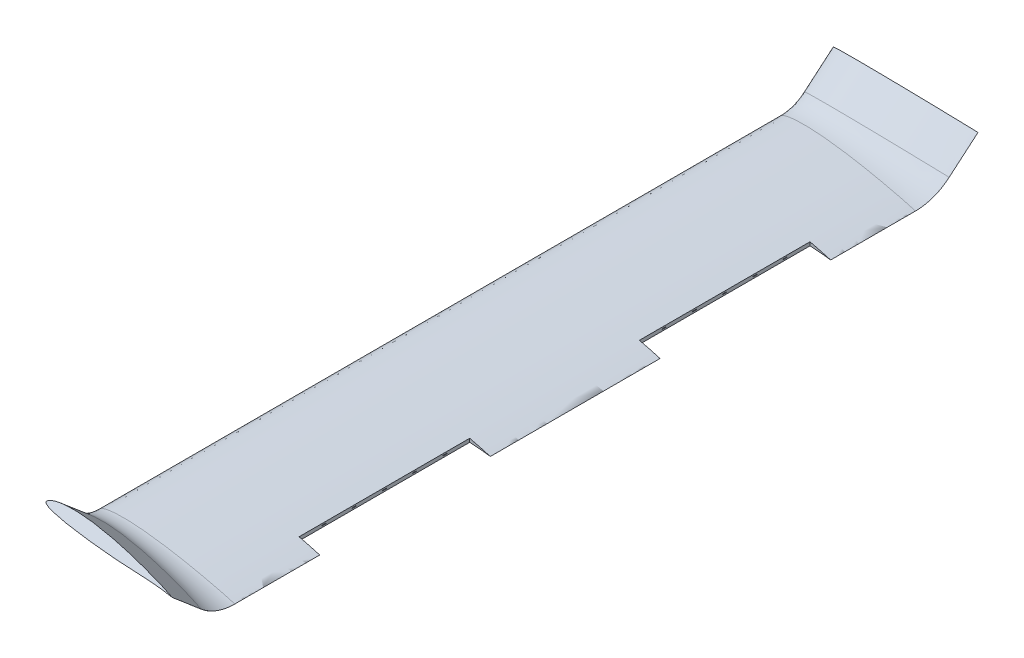
SolidWorks part; units mm, degrees
material "Bambu PETG Basic"
ref_plane "Front Plane" through (0, 0, 0) normal (0, 0, 1) x (1, 0, 0)
ref_plane "Top Plane" through (0, 0, 0) normal (0, 1, 0) x (1, 0, 0)
ref_plane "Right Plane" through (0, 0, 0) normal (1, 0, 0) x (0, 0, -1)
curve "Curve1"
  spline degree 3 poles (119.1315, 0.0649, 0) (120.2156, -0.0244, 0) (119.1768, 0.1241, 0) (118.3611, 0.3045, 0) (116.4409, 0.6648, 0) (114.1217, 1.0784, 0) (111.1249, 1.5376, 0) (107.6046, 2.0509, 0) (103.5602, 2.608, 0) (99.06, 3.1954, 0) (94.1552, 3.7992, 0) (88.9062, 4.4027, 0) (83.3727, 4.9915, 0) (77.618, 5.549, 0) (71.7044, 6.061, 0) (65.6958, 6.5098, 0) (59.6548, 6.8864, 0) (53.6439, 7.1734, 0) (47.7232, 7.3639, 0) (41.951, 7.4465, 0) (36.3826, 7.4159, 0) (31.0697, 7.2693, 0) (26.0605, 7.0029, 0) (21.3986, 6.6205, 0) (17.1237, 6.1259, 0) (13.271, 5.5293, 0) (9.8698, 4.8453, 0) (6.9483, 4.0868, 0) (4.5212, 3.2757, 0) (2.6143, 2.4295, 0) (1.2014, 1.5823, 0) (0.3641, 0.7994, 0) (-0.0092, 0.2127, 0) (0.0098, -0.2759, 0) (0.5281, -0.822, 0) (1.6534, -1.2926, 0) (3.3836, -1.8053, 0) (5.6974, -2.226, 0) (8.5941, -2.5892, 0) (12.0482, -2.8762, 0) (16.0312, -3.0928, 0) (20.503, -3.242, 0) (25.4176, -3.3266, 0) (30.7212, -3.3509, 0) (36.3546, -3.3217, 0) (42.254, -3.2414, 0) (48.3509, -3.1139, 0) (54.5739, -2.9419, 0) (60.8492, -2.7246, 0) (67.1164, -2.4479, 0) (73.3283, -2.0718, 0) (79.4439, -1.6435, 0) (85.4067, -1.2207, 0) (91.1384, -0.83, 0) (96.5553, -0.4959, 0) (101.5728, -0.229, 0) (106.1163, -0.0388, 0) (110.0944, 0.0802, 0) (113.4911, 0.1249, 0) (116.1071, 0.1318, 0) (118.2476, 0.0764, 0) (119.1315, 0.0649, 0) (120.2156, -0.0244, 0) (119.1768, 0.1241, 0) knots -0.014822 -0.00667 -0.001684 0 0.001648 0.006398 0.013891 0.023874 0.036301 0.051055 0.067935 0.086711 0.107144 0.128994 0.151997 0.175902 0.200434 0.225339 0.250352 0.275221 0.299694 0.323544 0.346547 0.368496 0.38921 0.408523 0.426284 0.442373 0.456684 0.46913 0.479656 0.488244 0.494928 0.499769 0.502616 0.502853 0.505768 0.510839 0.518187 0.527885 0.539915 0.554232 0.570707 0.589198 0.609515 0.631441 0.65473 0.679124 0.704341 0.730082 0.756046 0.781927 0.807595 0.83294 0.857679 0.881457 0.903929 0.924736 0.943553 0.960078 0.974032 0.985178 0.99333 0.998316 1 1.001648 1.006398 1.013891 periodic
sketch "Sketch2" plane through (0, 0, 0) normal (0, 0, 1) x (1, 0, 0)
  line L0 (0, 0) -> (119.3426, -12.5434) construction
  spline S2 degree 3 poles (147.8928, -15.4463) (149.4961, -15.7494) (147.9697, -15.3651) (146.7812, -14.9681) (143.9731, -14.1295) (140.5782, -13.1489) (136.1796, -11.994) (131.0085, -10.6763) (125.0626, -9.2111) (118.4414, -7.6292) (111.2191, -5.9594) (103.4834, -4.2361) (95.3209, -2.4902) (86.8235, -0.7562) (78.0821, 0.9348) (69.1889, 2.5464) (60.2361, 4.0555) (51.3141, 5.4261) (42.5116, 6.6385) (33.9137, 7.6667) (25.602, 8.4943) (17.6534, 9.1085) (10.1389, 9.4965) (3.1245, 9.6571) (-3.3303, 9.5895) (-9.1713, 9.3035) (-14.3523, 8.8165) (-18.8295, 8.143) (-22.5773, 7.3137) (-25.5548, 6.3502) (-27.7953, 5.308) (-29.1672, 4.2712) (-29.816, 3.4545) (-29.8643, 2.7228) (-29.1767, 1.8267) (-27.5718, 0.9483) (-25.0711, -0.0878) (-21.6854, -1.0781) (-17.421, -2.0741) (-12.3134, -3.0439) (-6.4055, -3.9916) (0.2421, -4.9153) (7.5604, -5.8121) (15.4683, -6.6798) (23.8767, -7.5195) (32.6899, -8.3247) (41.8052, -9.0905) (51.1155, -9.8097) (60.511, -10.4694) (69.9037, -11.0393) (79.2294, -11.4522) (88.4197, -11.7722) (97.3811, -12.0763) (105.9929, -12.3922) (114.1262, -12.7431) (121.653, -13.1316) (128.4607, -13.5603) (134.4139, -14.0065) (139.4881, -14.4724) (143.3916, -14.8723) (146.5761, -15.2905) (147.8928, -15.4463) (149.4961, -15.7494) (147.9697, -15.3651) knots -0.014822 -0.00667 -0.001684 0 0.001648 0.006398 0.013891 0.023874 0.036301 0.051055 0.067935 0.086711 0.107144 0.128994 0.151997 0.175902 0.200434 0.225339 0.250352 0.275221 0.299694 0.323544 0.346547 0.368496 0.38921 0.408523 0.426284 0.442373 0.456684 0.46913 0.479656 0.488244 0.494928 0.499769 0.502616 0.502853 0.505768 0.510839 0.518187 0.527885 0.539915 0.554232 0.570707 0.589198 0.609515 0.631441 0.65473 0.679124 0.704341 0.730082 0.756046 0.781927 0.807595 0.83294 0.857679 0.881457 0.903929 0.924736 0.943553 0.960078 0.974032 0.985178 0.99333 0.998316 1 1.001648 1.006398 1.013891 only from (149.1783, -15.6793) to (149.1783, -15.6793)
  point P1 (-29.8357, 3.1359)
extrude "Boss-Extrude1" add sketch "Sketch2" along normal blind 450 and the other way blind 450
ref_plane "Plane5" through (-29.8357, 0, 0) normal (1, 0, 0) x (0, 0, -1)
sketch "Sketch4" plane through (0, 0, 450) normal (0, 0, 1) x (1, 0, 0)
  spline S1 degree 3 poles (147.8928, -15.4463) (149.4961, -15.7494) (147.9697, -15.3651) (146.7812, -14.9681) (143.9731, -14.1295) (140.5782, -13.1489) (136.1796, -11.994) (131.0085, -10.6763) (125.0626, -9.2111) (118.4414, -7.6292) (111.2191, -5.9594) (103.4834, -4.2361) (95.3209, -2.4902) (86.8235, -0.7562) (78.0821, 0.9348) (69.1889, 2.5464) (60.2361, 4.0555) (51.3141, 5.4261) (42.5116, 6.6385) (33.9137, 7.6667) (25.602, 8.4943) (17.6534, 9.1085) (10.1389, 9.4965) (3.1245, 9.6571) (-3.3303, 9.5895) (-9.1713, 9.3035) (-14.3523, 8.8165) (-18.8295, 8.143) (-22.5773, 7.3137) (-25.5548, 6.3502) (-27.7953, 5.308) (-29.1672, 4.2712) (-29.816, 3.4545) (-29.8643, 2.7228) (-29.1767, 1.8267) (-27.5718, 0.9483) (-25.0711, -0.0878) (-21.6854, -1.0781) (-17.421, -2.0741) (-12.3134, -3.0439) (-6.4055, -3.9916) (0.2421, -4.9153) (7.5604, -5.8121) (15.4683, -6.6798) (23.8767, -7.5195) (32.6899, -8.3247) (41.8052, -9.0905) (51.1155, -9.8097) (60.511, -10.4694) (69.9037, -11.0393) (79.2294, -11.4522) (88.4197, -11.7722) (97.3811, -12.0763) (105.9929, -12.3922) (114.1262, -12.7431) (121.653, -13.1316) (128.4607, -13.5603) (134.4139, -14.0065) (139.4881, -14.4724) (143.3916, -14.8723) (146.5761, -15.2905) (147.8928, -15.4463) (149.4961, -15.7494) (147.9697, -15.3651) knots -0.014822 -0.00667 -0.001684 0 0.001648 0.006398 0.013891 0.023874 0.036301 0.051055 0.067935 0.086711 0.107144 0.128994 0.151997 0.175902 0.200434 0.225339 0.250352 0.275221 0.299694 0.323544 0.346547 0.368496 0.38921 0.408523 0.426284 0.442373 0.456684 0.46913 0.479656 0.488244 0.494928 0.499769 0.502616 0.502853 0.505768 0.510839 0.518187 0.527885 0.539915 0.554232 0.570707 0.589198 0.609515 0.631441 0.65473 0.679124 0.704341 0.730082 0.756046 0.781927 0.807595 0.83294 0.857679 0.881457 0.903929 0.924736 0.943553 0.960078 0.974032 0.985178 0.99333 0.998316 1 1.001648 1.006398 1.013891 only from (149.1783, -15.6793) to (149.1783, -15.6793)
  spline S3 degree 3 poles (147.8928, -15.4463) (149.4961, -15.7494) (147.9697, -15.3651) (146.7812, -14.9681) (143.9731, -14.1295) (140.5782, -13.1489) (136.1796, -11.994) (131.0085, -10.6763) (125.0626, -9.2111) (118.4414, -7.6292) (111.2191, -5.9594) (103.4834, -4.2361) (95.3209, -2.4902) (86.8235, -0.7562) (78.0821, 0.9348) (69.1889, 2.5464) (60.2361, 4.0555) (51.3141, 5.4261) (42.5116, 6.6385) (33.9137, 7.6667) (25.602, 8.4943) (17.6534, 9.1085) (10.1389, 9.4965) (3.1245, 9.6571) (-3.3303, 9.5895) (-9.1713, 9.3035) (-14.3523, 8.8165) (-18.8295, 8.143) (-22.5773, 7.3137) (-25.5548, 6.3502) (-27.7953, 5.308) (-29.1672, 4.2712) (-29.816, 3.4545) (-29.8643, 2.7228) (-29.1767, 1.8267) (-27.5718, 0.9483) (-25.0711, -0.0878) (-21.6854, -1.0781) (-17.421, -2.0741) (-12.3134, -3.0439) (-6.4055, -3.9916) (0.2421, -4.9153) (7.5604, -5.8121) (15.4683, -6.6798) (23.8767, -7.5195) (32.6899, -8.3247) (41.8052, -9.0905) (51.1155, -9.8097) (60.511, -10.4694) (69.9037, -11.0393) (79.2294, -11.4522) (88.4197, -11.7722) (97.3811, -12.0763) (105.9929, -12.3922) (114.1262, -12.7431) (121.653, -13.1316) (128.4607, -13.5603) (134.4139, -14.0065) (139.4881, -14.4724) (143.3916, -14.8723) (146.5761, -15.2905) (147.8928, -15.4463) (149.4961, -15.7494) (147.9697, -15.3651) knots -0.014822 -0.00667 -0.001684 0 0.001648 0.006398 0.013891 0.023874 0.036301 0.051055 0.067935 0.086711 0.107144 0.128994 0.151997 0.175902 0.200434 0.225339 0.250352 0.275221 0.299694 0.323544 0.346547 0.368496 0.38921 0.408523 0.426284 0.442373 0.456684 0.46913 0.479656 0.488244 0.494928 0.499769 0.502616 0.502853 0.505768 0.510839 0.518187 0.527885 0.539915 0.554232 0.570707 0.589198 0.609515 0.631441 0.65473 0.679124 0.704341 0.730082 0.756046 0.781927 0.807595 0.83294 0.857679 0.881457 0.903929 0.924736 0.943553 0.960078 0.974032 0.985178 0.99333 0.998316 1 1.001648 1.006398 1.013891 only from (149.1783, -15.6793) to (149.1783, -15.6793)
  dimension "D1" = 0
sketch "Sketch5" plane through (-29.8357, 0, 0) normal (1, 0, 0) x (0, 0, -1)
  line L0 (0, 3.1359) -> (-541.8192, 3.1359) construction
  line L1 (55, 0) -> (-55, 0) construction
  line L2 (-482.3366, 15) -> (-520.4725, 47.3366)
  arc A0 (-450, 3.1359) -> (-482.3366, 15) centre (-450, 53.1359) cw
  point P0 (-450, 3.1359)
  dimension "D1" = 15
  dimension "D2" = 50
  dimension "D3" = 50
ref_plane "Plane6" through (0, 3.1359, 0) normal (0, 1, 0) x (1, 0, 0)
sweep "Sweep1" add profiles "Sketch4" path "Sketch5"
mirror "Mirror1" about plane through (0, 0, 0) normal (0, 0, 1) of "Sweep1"
ref_plane "Plane7" through (0, 0, 2) normal (0, 0, 1) x (1, 0, 0)
sketch "Sketch6" plane through (0, 0, 2) normal (0, 0, 1) x (1, 0, 0)
  line L0 (0, 0) -> (119.3426, -12.5434) construction
  line L1 (0, 0) -> (119.3426, -12.5434) construction
ref_plane "Plane8" through (0, 0, 0) normal (-0.1045, -0.9945, 0) x (-0.9945, 0.1045, 0)
sketch "Sketch7" plane through (0, 0, 0) normal (-0.1045, -0.9945, 0) x (-0.9945, 0.1045, 0)
  line L0 (-150, 0) -> (30, 0) construction
  line L1 (-60.5, 7.625) -> (-14.5, 7.625)
  line L2 (-60.5, 7.625) -> (-60.5, -7.625)
  line L3 (-60.5, -7.625) -> (-14.5, -7.625)
  line L4 (-14.5, 7.625) -> (-14.5, -7.625)
  point P4 (-14.5, 0)
  dimension "D1" = 46
  dimension "D2" = 15.25
  dimension "D3" = 44.5
extrude "Cut-Extrude1" cut sketch "Sketch7" along normal through all contours L1 L4 L3 L2
sketch "Sketch8" plane through (14.4206, -1.5157, 0) normal (0.9945, -0.1045, 0) x (0, 0, -1)
  line L4 (-7.625, -5.012) -> (7.625, -5.012)
  line L5 (7.625, -5.012) -> (7.625, 0)
  line L6 (7.625, 0) -> (-7.625, 0)
  line L7 (-7.625, 0) -> (-7.625, -5.012)
  line L8 (-7.625, -5.012) -> (7.625, -5.012)
  line L9 (7.625, -5.012) -> (7.625, 0)
  line L10 (7.625, 0) -> (-7.625, 0)
  line L11 (-7.625, 0) -> (-7.625, -5.012)
  dimension "D1" = 0
extrude "Cut-Extrude2" cut sketch "Sketch8" against normal through all
ref_plane "Plane9" through (0, 0, 250) normal (0, 0, 1) x (1, 0, 0)
sketch "Sketch10" plane through (0, 0, 250) normal (0, 0, 1) x (1, 0, 0)
  line L0 (21.6866, -7.2956) -> (22.642, 4.6664)
  line L1 (22.642, 4.6664) -> (65.0071, 1.2827)
  line L2 (65.0071, 1.2827) -> (64.0517, -10.6792)
  spline S0 degree 3 poles (-29.8357, 3.1359) (-29.8389, 3.1072) (-29.8643, 2.7228) (-29.1767, 1.8267) (-27.5718, 0.9483) (-25.0711, -0.0878) (-21.6854, -1.0781) (-17.421, -2.0741) (-12.3134, -3.0439) (-6.4055, -3.9916) (0.2421, -4.9153) (7.5604, -5.8121) (15.4683, -6.6798) (23.8767, -7.5195) (32.6899, -8.3247) (41.8052, -9.0905) (50.8549, -9.7896) (56.8555, -10.2127) (59.7398, -10.4037) knots 0.502616 0.502616 0.502616 0.502616 0.502853 0.505768 0.510839 0.518187 0.527885 0.539915 0.554232 0.570707 0.589198 0.609515 0.631441 0.65473 0.679124 0.704341 0.730082 0.753894 0.753894 0.753894 0.753894 construction
  spline S1 degree 3 poles (147.8928, -15.4463) (149.4961, -15.7494) (147.9697, -15.3651) (146.7812, -14.9681) (143.9731, -14.1295) (140.5782, -13.1489) (136.1796, -11.994) (131.0085, -10.6763) (125.0626, -9.2111) (118.4414, -7.6292) (111.2191, -5.9594) (103.4834, -4.2361) (95.3209, -2.4902) (86.8235, -0.7562) (78.0821, 0.9348) (69.1889, 2.5464) (60.2361, 4.0555) (51.3141, 5.4261) (42.5116, 6.6385) (33.9137, 7.6667) (25.602, 8.4943) (17.6534, 9.1085) (10.1389, 9.4965) (3.1245, 9.6571) (-3.3303, 9.5895) (-9.1713, 9.3035) (-14.3523, 8.8165) (-18.8295, 8.143) (-22.5773, 7.3137) (-25.5548, 6.3502) (-27.7953, 5.308) (-29.1672, 4.2712) (-29.816, 3.4545) (-29.8643, 2.7228) (-29.1767, 1.8267) (-27.5718, 0.9483) (-25.0711, -0.0878) (-21.6854, -1.0781) (-17.421, -2.0741) (-12.3134, -3.0439) (-6.4055, -3.9916) (0.2421, -4.9153) (7.5604, -5.8121) (15.4683, -6.6798) (23.8767, -7.5195) (32.6899, -8.3247) (41.8052, -9.0905) (51.1155, -9.8097) (60.511, -10.4694) (69.9037, -11.0393) (79.2294, -11.4522) (88.4197, -11.7722) (97.3811, -12.0763) (105.9929, -12.3922) (114.1262, -12.7431) (121.653, -13.1316) (128.4607, -13.5603) (134.4139, -14.0065) (139.4881, -14.4724) (143.3916, -14.8723) (146.5761, -15.2905) (147.8928, -15.4463) (149.4961, -15.7494) (147.9697, -15.3651) knots -0.014822 -0.00667 -0.001684 0 0.001648 0.006398 0.013891 0.023874 0.036301 0.051055 0.067935 0.086711 0.107144 0.128994 0.151997 0.175902 0.200434 0.225339 0.250352 0.275221 0.299694 0.323544 0.346547 0.368496 0.38921 0.408523 0.426284 0.442373 0.456684 0.46913 0.479656 0.488244 0.494928 0.499769 0.502616 0.502853 0.505768 0.510839 0.518187 0.527885 0.539915 0.554232 0.570707 0.589198 0.609515 0.631441 0.65473 0.679124 0.704341 0.730082 0.756046 0.781927 0.807595 0.83294 0.857679 0.881457 0.903929 0.924736 0.943553 0.960078 0.974032 0.985178 0.99333 0.998316 1 1.001648 1.006398 1.013891 only from (149.1783, -15.6793) to (149.1783, -15.6793) construction
  spline S3 degree 3 poles (147.8928, -15.4463) (149.4961, -15.7494) (147.9697, -15.3651) (146.7812, -14.9681) (143.9731, -14.1295) (140.5782, -13.1489) (136.1796, -11.994) (131.0085, -10.6763) (125.0626, -9.2111) (118.4414, -7.6292) (111.2191, -5.9594) (103.4834, -4.2361) (95.3209, -2.4902) (86.8235, -0.7562) (78.0821, 0.9348) (69.1889, 2.5464) (60.2361, 4.0555) (51.3141, 5.4261) (42.5116, 6.6385) (33.9137, 7.6667) (25.602, 8.4943) (17.6534, 9.1085) (10.1389, 9.4965) (3.1245, 9.6571) (-3.3303, 9.5895) (-9.1713, 9.3035) (-14.3523, 8.8165) (-18.8295, 8.143) (-22.5773, 7.3137) (-25.5548, 6.3502) (-27.7953, 5.308) (-29.1672, 4.2712) (-29.816, 3.4545) (-29.8643, 2.7228) (-29.1767, 1.8267) (-27.5718, 0.9483) (-25.0711, -0.0878) (-21.6854, -1.0781) (-17.421, -2.0741) (-12.3134, -3.0439) (-6.4055, -3.9916) (0.2421, -4.9153) (7.5604, -5.8121) (15.4683, -6.6798) (23.8767, -7.5195) (32.6899, -8.3247) (41.8052, -9.0905) (51.1155, -9.8097) (60.511, -10.4694) (69.9037, -11.0393) (79.2294, -11.4522) (88.4197, -11.7722) (97.3811, -12.0763) (105.9929, -12.3922) (114.1262, -12.7431) (121.653, -13.1316) (128.4607, -13.5603) (134.4139, -14.0065) (139.4881, -14.4724) (143.3916, -14.8723) (146.5761, -15.2905) (147.8928, -15.4463) (149.4961, -15.7494) (147.9697, -15.3651) knots -0.014822 -0.00667 -0.001684 0 0.001648 0.006398 0.013891 0.023874 0.036301 0.051055 0.067935 0.086711 0.107144 0.128994 0.151997 0.175902 0.200434 0.225339 0.250352 0.275221 0.299694 0.323544 0.346547 0.368496 0.38921 0.408523 0.426284 0.442373 0.456684 0.46913 0.479656 0.488244 0.494928 0.499769 0.502616 0.502853 0.505768 0.510839 0.518187 0.527885 0.539915 0.554232 0.570707 0.589198 0.609515 0.631441 0.65473 0.679124 0.704341 0.730082 0.756046 0.781927 0.807595 0.83294 0.857679 0.881457 0.903929 0.924736 0.943553 0.960078 0.974032 0.985178 0.99333 0.998316 1 1.001648 1.006398 1.013891 only from (149.1783, -15.6793) to (149.1783, -15.6793)
  spline S4 degree 3 poles (147.8928, -15.4463) (149.4961, -15.7494) (147.9697, -15.3651) (146.7812, -14.9681) (143.9731, -14.1295) (140.5782, -13.1489) (136.1796, -11.994) (131.0085, -10.6763) (125.0626, -9.2111) (118.4414, -7.6292) (111.2191, -5.9594) (103.4834, -4.2361) (95.3209, -2.4902) (86.8235, -0.7562) (78.0821, 0.9348) (69.1889, 2.5464) (60.2361, 4.0555) (51.3141, 5.4261) (42.5116, 6.6385) (33.9137, 7.6667) (25.602, 8.4943) (17.6534, 9.1085) (10.1389, 9.4965) (3.1245, 9.6571) (-3.3303, 9.5895) (-9.1713, 9.3035) (-14.3523, 8.8165) (-18.8295, 8.143) (-22.5773, 7.3137) (-25.5548, 6.3502) (-27.7953, 5.308) (-29.1672, 4.2712) (-29.816, 3.4545) (-29.8643, 2.7228) (-29.1767, 1.8267) (-27.5718, 0.9483) (-25.0711, -0.0878) (-21.6854, -1.0781) (-17.421, -2.0741) (-12.3134, -3.0439) (-6.4055, -3.9916) (0.2421, -4.9153) (7.5604, -5.8121) (15.4683, -6.6798) (23.8767, -7.5195) (32.6899, -8.3247) (41.8052, -9.0905) (51.1155, -9.8097) (60.511, -10.4694) (69.9037, -11.0393) (79.2294, -11.4522) (88.4197, -11.7722) (97.3811, -12.0763) (105.9929, -12.3922) (114.1262, -12.7431) (121.653, -13.1316) (128.4607, -13.5603) (134.4139, -14.0065) (139.4881, -14.4724) (143.3916, -14.8723) (146.5761, -15.2905) (147.8928, -15.4463) (149.4961, -15.7494) (147.9697, -15.3651) knots -0.014822 -0.00667 -0.001684 0 0.001648 0.006398 0.013891 0.023874 0.036301 0.051055 0.067935 0.086711 0.107144 0.128994 0.151997 0.175902 0.200434 0.225339 0.250352 0.275221 0.299694 0.323544 0.346547 0.368496 0.38921 0.408523 0.426284 0.442373 0.456684 0.46913 0.479656 0.488244 0.494928 0.499769 0.502616 0.502853 0.505768 0.510839 0.518187 0.527885 0.539915 0.554232 0.570707 0.589198 0.609515 0.631441 0.65473 0.679124 0.704341 0.730082 0.756046 0.781927 0.807595 0.83294 0.857679 0.881457 0.903929 0.924736 0.943553 0.960078 0.974032 0.985178 0.99333 0.998316 1 1.001648 1.006398 1.013891 only from (149.1783, -15.6793) to (149.1783, -15.6793)
  dimension "D1" = 12
  dimension "D2" = 12
  dimension "D4" = 42.5
  dimension "D5" = 0
  dimension "D3" = 52.5
extrude "Cut-Extrude3" cut sketch "Sketch10" against normal blind 45 contours L0 S4 L2 L1 region at (43.3423, -3.0665, 250)
mirror "Mirror2" about plane through (0, 0, 0) normal (0, 0, 1) of "Cut-Extrude3"
sketch "Sketch11" plane through (0, 0, 205) normal (0, 0, 1) x (1, 0, 0)
  line L0 (48.4003, 0.6027) -> (63.3526, -0.5916)
  line L1 (48.4003, 0.6027) -> (48.0818, -3.3846)
  line L2 (63.3526, -0.5916) -> (63.0342, -4.5789)
  line L3 (48.0818, -3.3846) -> (63.0342, -4.5789)
  line L4 (22.642, 4.6664) -> (65.0071, 1.2827) construction
  line L5 (65.0071, 1.2827) -> (64.0517, -10.6792) construction
  dimension "D1" = 15
  dimension "D2" = 4
  dimension "D3" = 1.5
  dimension "D4" = 2
extrude "Cut-Extrude4" cut sketch "Sketch11" against normal blind 410 contours L0 L2 L3 L1
sketch "Sketch12" plane through (0, 0, 0) normal (-0.1045, -0.9945, 0) x (0.9945, -0.1045, 0)
  line L0 (37.4329, 0) -> (-37.4329, 0) construction
  line L1 (50, -7.625) -> (60.5, -7.625)
  line L2 (50, -7.625) -> (50, 7.625)
  line L3 (50, 7.625) -> (60.5, 7.625)
  line L4 (60.5, -7.625) -> (60.5, 7.625)
  line L5 (50, -7.625) -> (60.5, 7.625) construction
  line L6 (50, 7.625) -> (60.5, -7.625) construction
  line L7 (-30, 7.625) -> (-30, -7.625) construction
  line L8 (-30, 7.625) -> (60.5, 7.625) construction
  line L9 (60.5, -7.625) -> (60.5, 7.625) construction
  point P0 (55.25, 0)
  dimension "D3" = 80
extrude "Cut-Extrude5" cut sketch "Sketch12" against normal up to surface (5.7068 mm away) up to face at (55.8765, 0.0056, 0)
sketch "Sketch13" plane through (0, 0, 0) normal (0, 0, 1) x (1, 0, 0)
  line L0 (149.1783, -15.6793) -> (-29.8357, 3.1359) construction
  line L1 (149.1783, -15.6793) -> (149.1783, 0.6494) construction
  line L2 (10.1543, 0.9438) -> (4.7839, 1.5082)
  line L3 (10.1543, 0.9438) -> (10.7187, 6.3142)
  line L4 (4.7839, 1.5082) -> (5.3483, 6.8786)
  line L5 (10.7187, 6.3142) -> (5.3483, 6.8786)
  circle A0 centre (74.8919, -5.3577) radius 4.2
  dimension "D1" = 8.4
  dimension "D2" = 2.5
  dimension "D3" = 75
  dimension "D6" = 2
  dimension "D7" = 40
extrude "Cut-Extrude6" cut sketch "Sketch13" against normal blind 455 and the other way blind 455
fillet "Fillet1" radius 0.5 1 edges at (-29.8357, 3.1359, 0)
sketch "Sketch14" plane through (0, 0, 0) normal (0, 1, 0) x (1, 0, 0)
  line L0 (149.1783, -450) -> (149.1783, 450) construction
  line L1 (149.1783, 337.8) -> (121.8783, 337.8)
  line L2 (149.1783, 337.8) -> (149.1783, 112.2)
  line L3 (149.1783, 112.2) -> (121.8783, 112.2)
  line L4 (121.8783, 337.8) -> (121.8783, 112.2)
  line L5 (23.9037, 0) -> (23.9037, 450) construction
  line L6 (-37.4329, 0) -> (37.4329, 0) construction
  line L7 (149.1783, 450) -> (-29.8411, 450) construction
  line L8 (121.8783, -337.8) -> (121.8783, -112.2)
  line L9 (149.1783, -112.2) -> (121.8783, -112.2)
  line L10 (149.1783, -337.8) -> (149.1783, -112.2)
  line L11 (149.1783, -337.8) -> (121.8783, -337.8)
  point P12 (23.9037, 225)
  point P13 (121.8783, 225)
  dimension "D1" = 27.3
  dimension "D2" = 225.6
extrude "Cut-Extrude7" cut sketch "Sketch14" against normal through all both and the other way through all
sketch "Sketch15" plane through (121.8783, 0, 0) normal (1, 0, 0) x (0, 0, -1)
  line L0 (-225, -8.4524) -> (-225, -13.1582) construction
  line L1 (-112.2, -8.4524) -> (-337.8, -8.4524) construction
  line L2 (-337.8, -13.1582) -> (-112.2, -13.1582) construction
  line L3 (-187.65, -11.2053) -> (-182.35, -11.2053)
  line L4 (-227.65, -11.2053) -> (-222.35, -11.2053)
  line L5 (-227.65, -11.2053) -> (-227.65, -10.4053)
  line L6 (-227.65, -10.4053) -> (-222.35, -10.4053)
  line L7 (-222.35, -11.2053) -> (-222.35, -10.4053)
  line L8 (-227.65, -11.2053) -> (-222.35, -10.4053) construction
  line L9 (-227.65, -10.4053) -> (-222.35, -11.2053) construction
  line L10 (-187.65, -11.2053) -> (-187.65, -10.4053)
  line L11 (-187.65, -10.4053) -> (-182.35, -10.4053)
  line L12 (-182.35, -11.2053) -> (-182.35, -10.4053)
  line L13 (-185, -8.4524) -> (-185, -13.1582) construction
  line L14 (-187.65, -11.2053) -> (-182.35, -10.4053) construction
  line L15 (-187.65, -10.4053) -> (-182.35, -11.2053) construction
  line L16 (-147.65, -11.2053) -> (-142.35, -11.2053)
  line L17 (-147.65, -11.2053) -> (-147.65, -10.4053)
  line L18 (-147.65, -10.4053) -> (-142.35, -10.4053)
  line L19 (-142.35, -11.2053) -> (-142.35, -10.4053)
  line L20 (-145, -8.4524) -> (-145, -13.1582) construction
  line L21 (-147.65, -11.2053) -> (-142.35, -10.4053) construction
  line L22 (-147.65, -10.4053) -> (-142.35, -11.2053) construction
  line L23 (-267.65, -11.2053) -> (-262.35, -11.2053)
  line L24 (-267.65, -11.2053) -> (-267.65, -10.4053)
  line L25 (-267.65, -10.4053) -> (-262.35, -10.4053)
  line L26 (-262.35, -11.2053) -> (-262.35, -10.4053)
  line L27 (-265, -8.4524) -> (-265, -13.1582) construction
  line L28 (-267.65, -11.2053) -> (-262.35, -10.4053) construction
  line L29 (-267.65, -10.4053) -> (-262.35, -11.2053) construction
  line L30 (-307.65, -11.2053) -> (-302.35, -11.2053)
  line L31 (-307.65, -11.2053) -> (-307.65, -10.4053)
  line L32 (-307.65, -10.4053) -> (-302.35, -10.4053)
  line L33 (-302.35, -11.2053) -> (-302.35, -10.4053)
  line L34 (-305, -8.4524) -> (-305, -13.1582) construction
  line L35 (-307.65, -11.2053) -> (-302.35, -10.4053) construction
  line L36 (-307.65, -10.4053) -> (-302.35, -11.2053) construction
  line L37 (0, 37.4329) -> (0, -37.4329) construction
  line L38 (307.65, -10.4053) -> (302.35, -11.2053) construction
  line L39 (307.65, -11.2053) -> (302.35, -10.4053) construction
  line L40 (305, -8.4524) -> (305, -13.1582) construction
  line L41 (267.65, -10.4053) -> (262.35, -11.2053) construction
  line L42 (267.65, -11.2053) -> (262.35, -10.4053) construction
  line L43 (265, -8.4524) -> (265, -13.1582) construction
  line L44 (147.65, -10.4053) -> (142.35, -11.2053) construction
  line L45 (147.65, -11.2053) -> (142.35, -10.4053) construction
  line L46 (145, -8.4524) -> (145, -13.1582) construction
  line L47 (187.65, -10.4053) -> (182.35, -11.2053) construction
  line L48 (187.65, -11.2053) -> (182.35, -10.4053) construction
  line L49 (185, -8.4524) -> (185, -13.1582) construction
  line L50 (227.65, -10.4053) -> (222.35, -11.2053) construction
  line L51 (227.65, -11.2053) -> (222.35, -10.4053) construction
  line L52 (225, -8.4524) -> (225, -13.1582) construction
  line L53 (302.35, -11.2053) -> (302.35, -10.4053)
  line L54 (307.65, -10.4053) -> (302.35, -10.4053)
  line L55 (307.65, -11.2053) -> (307.65, -10.4053)
  line L56 (307.65, -11.2053) -> (302.35, -11.2053)
  line L57 (262.35, -11.2053) -> (262.35, -10.4053)
  line L58 (267.65, -10.4053) -> (262.35, -10.4053)
  line L59 (267.65, -11.2053) -> (267.65, -10.4053)
  line L60 (267.65, -11.2053) -> (262.35, -11.2053)
  line L61 (142.35, -11.2053) -> (142.35, -10.4053)
  line L62 (147.65, -10.4053) -> (142.35, -10.4053)
  line L63 (147.65, -11.2053) -> (147.65, -10.4053)
  line L64 (147.65, -11.2053) -> (142.35, -11.2053)
  line L65 (182.35, -11.2053) -> (182.35, -10.4053)
  line L66 (187.65, -10.4053) -> (182.35, -10.4053)
  line L67 (187.65, -11.2053) -> (187.65, -10.4053)
  line L68 (222.35, -11.2053) -> (222.35, -10.4053)
  line L69 (227.65, -10.4053) -> (222.35, -10.4053)
  line L70 (227.65, -11.2053) -> (227.65, -10.4053)
  line L71 (227.65, -11.2053) -> (222.35, -11.2053)
  line L72 (187.65, -11.2053) -> (182.35, -11.2053)
  point P6 (-225, -10.8053)
  point P14 (-185, -10.8053)
  point P21 (-145, -10.8053)
  point P28 (-265, -10.8053)
  point P35 (-305, -10.8053)
  point P71 (305, -10.8053)
  point P72 (265, -10.8053)
  point P73 (145, -10.8053)
  point P74 (185, -10.8053)
  point P75 (225, -10.8053)
  dimension "D1" = 5.3
  dimension "D2" = 0.8
  dimension "D4" = 34.7
  dimension "D6" = 34.7
  dimension "D3" = 3
  dimension "D5" = 3
extrude "Cut-Extrude8" cut sketch "Sketch15" against normal blind 5
chamfer "Chamfer1" distance 1 angle 45 4 edges at (55.1393, -3.9483, -7.625) (60.3743, -4.3664, 0) (49.9044, -3.5302, 0) (55.1393, -3.9483, 7.625) first distance on face at (19.3874, -1.5892, -7.625) first distance on face at (60.0571, -7.385, 0) first distance on face at (49.8152, -4.3783, 0) first distance on face at (19.3874, -1.5892, 7.625)
